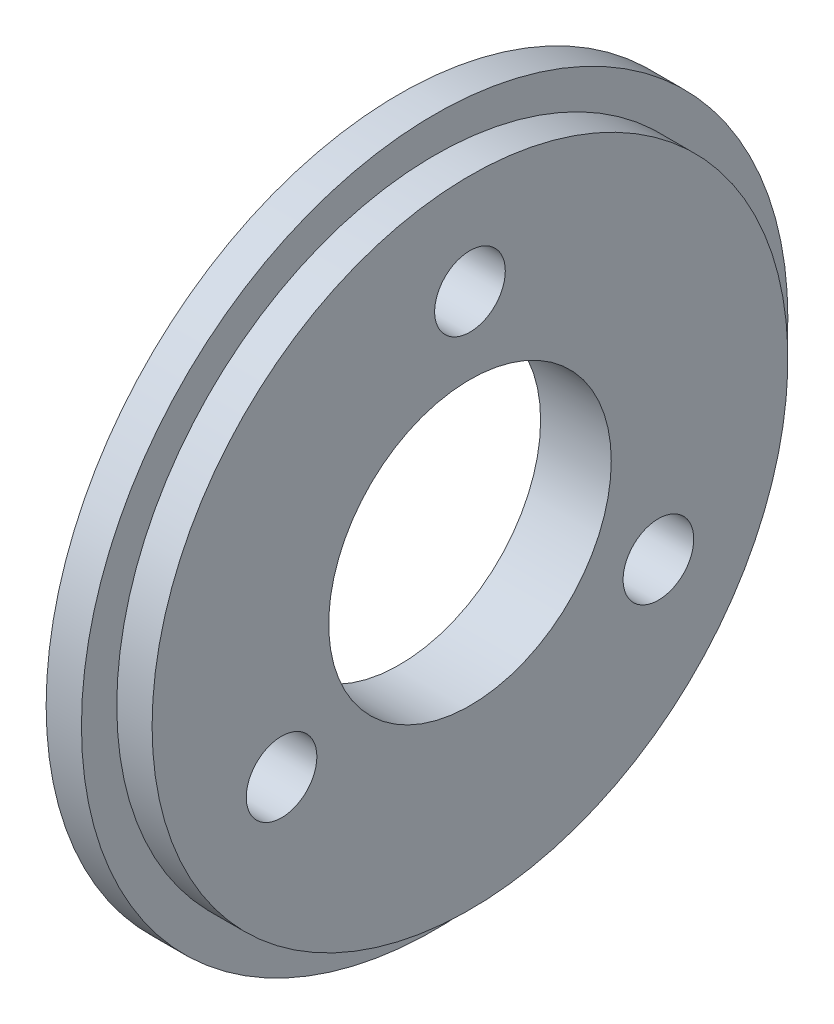
SolidWorks part; units mm, degrees
ref_plane "Front Plane" through (0, 0, 0) normal (0, 0, 1) x (1, 0, 0)
ref_plane "Top Plane" through (0, 0, 0) normal (0, 1, 0) x (1, 0, 0)
ref_plane "Right Plane" through (0, 0, 0) normal (1, 0, 0) x (0, 0, -1)
sketch "Sketch1" plane through (0, 0, 0) normal (0, 0, 1) x (1, 0, 0)
  line L0 (0, 0) -> (0, 57.15)
  line L1 (0, 57.15) -> (-6.35, 57.15)
  line L2 (-6.35, 57.15) -> (-6.35, 63.5)
  line L3 (-6.35, 63.5) -> (-12.7, 63.5)
  line L4 (-12.7, 63.5) -> (-12.7, 0)
  line L5 (0, 0) -> (50000, 0) construction
  line L6 (0, 0) -> (-12.7, 0)
  dimension "D1" = 57.15
  dimension "D2" = 63.5
  dimension "D3" = 6.35
  dimension "D4" = 12.7
revolve "Revolve1" add sketch "Sketch1" angle 360 about L5
sketch "Sketch4" plane through (0, 0, 0) normal (1, 0, 0) x (0, 0, -1)
  line L0 (0, 0) -> (0, 39.116) construction
  circle A0 centre (0, 39.116) radius 3.4925
  circle A1 centre (33.8754, -19.558) radius 3.4925
  circle A2 centre (-33.8754, -19.558) radius 3.4925
  circle A3 centre (0, 39.116) radius 6.35
  circle A4 centre (33.8754, -19.558) radius 6.35
  circle A5 centre (-33.8754, -19.558) radius 6.35
  circle A6 centre (0, 0) radius 25.4
  point P11 (0, 0)
  point P16 (0, 0)
  dimension "D2" = 6.985
  dimension "D4" = 12.7
  dimension "D6" = 50.8
  dimension "D1" = 39.116
  dimension "D3" = 3
  dimension "D5" = 3
extrude "Cut-Extrude1" cut sketch "Sketch4" against normal through all contours A0 | A1 | A2 | A6 region at (0, 39.116, 0) region at (0, -19.558, -33.8754) region at (0, -19.558, 33.8754) region at (0, 0, 0)
extrude "Cut-Extrude2" cut sketch "Sketch4<3>" against normal blind 10.16 contours A3 A0 | A4 A1 | A5 A2 region at (0, 39.116, 6.1704) region at (0, -19.558, -27.7051) region at (0, -19.558, 40.0458)
sketch "Sketch4<3>" plane through (0, 0, 0) normal (1, 0, 0) x (0, 0, -1) same geometry as "Sketch4"
